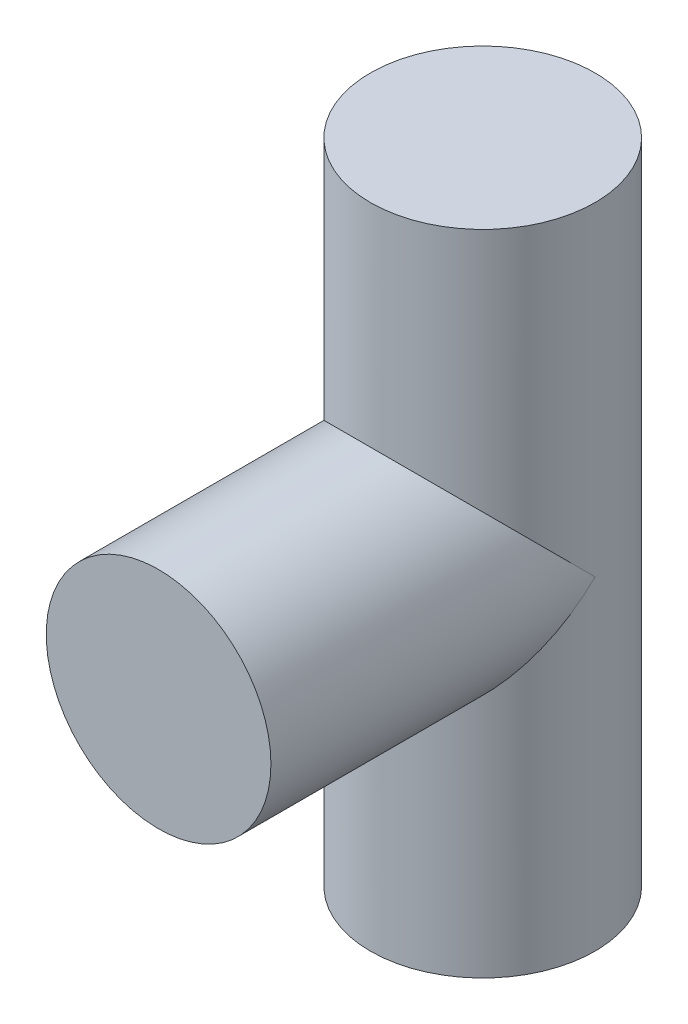
SolidWorks part; units mm, degrees
material "Brass"
ref_plane "Front Plane" through (0, 0, 0) normal (0, 0, 1) x (1, 0, 0)
ref_plane "Top Plane" through (0, 0, 0) normal (0, 1, 0) x (1, 0, 0)
ref_plane "Right Plane" through (0, 0, 0) normal (1, 0, 0) x (0, 0, -1)
sketch "Sketch1" plane through (0, 0, 0) normal (0, 1, 0) x (1, 0, 0)
  circle A0 centre (0, 0) radius 12.5
  dimension "D1" = 25
extrude "Boss-Extrude1" add sketch "Sketch1" along normal blind 36.068 and the other way blind 36.068
sketch "Sketch2" plane through (0, 0, 0) normal (0, 0, 1) x (1, 0, 0)
  circle A0 centre (0, 0) radius 12.5
extrude "Boss-Extrude2" add sketch "Sketch2" along normal blind 36.068
